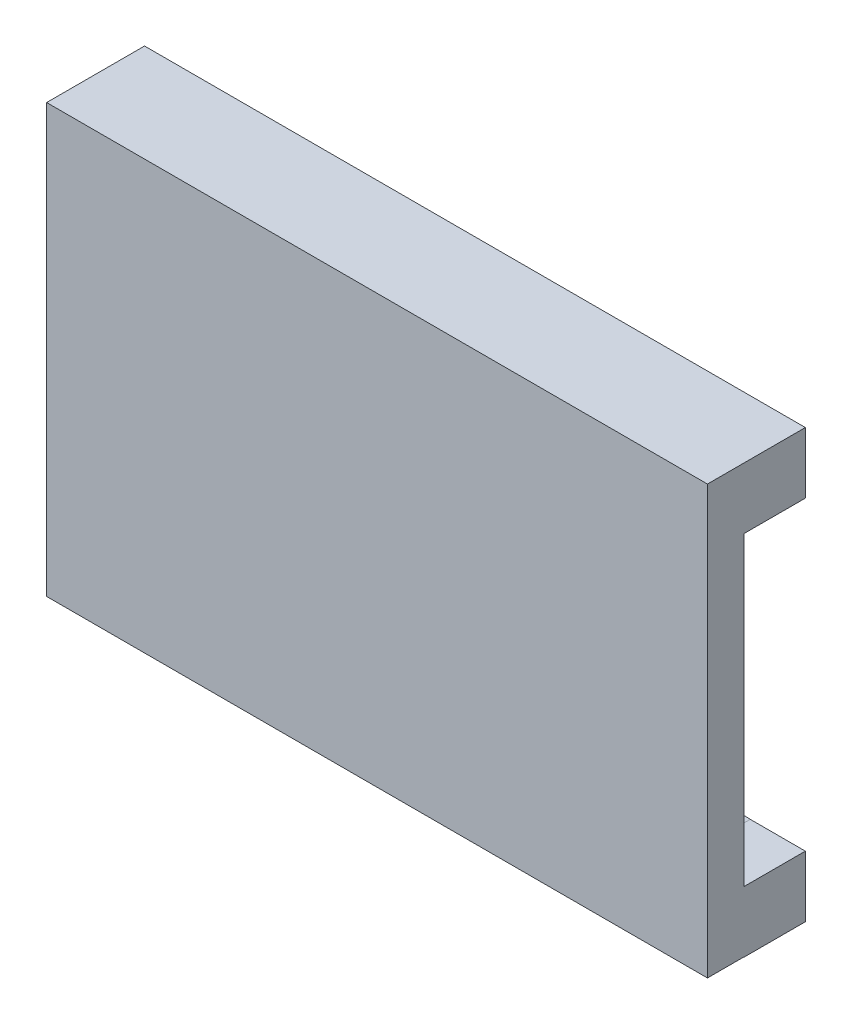
SolidWorks part; units mm, degrees
ref_plane "Front Plane" through (0, 0, 0) normal (0, 0, 1) x (1, 0, 0)
ref_plane "Top Plane" through (0, 0, 0) normal (0, 1, 0) x (1, 0, 0)
ref_plane "Right Plane" through (0, 0, 0) normal (1, 0, 0) x (0, 0, -1)
sketch "Sketch1" plane through (0, 0, 0) normal (0, 0, 1) x (1, 0, 0)
  line L0 (-7.25, 12.4789) -> (7.25, 12.4789) construction
  line L1 (27, -12.5) -> (-27, -12.5) construction
  line L2 (-27, 12.4789) -> (27, 12.4789)
  line L3 (27, -12.5) -> (-27, -12.5)
  line L4 (27, -12.5) -> (27, 12.4789)
  line L5 (-27, 12.4789) -> (-27, -12.5)
  circle A0 centre (-22.5, 0) radius 1.25 construction
  circle A1 centre (22.5, 0) radius 1.25 construction
  circle A2 centre (-22.5, 0) radius 1.25 construction
  circle A3 centre (22.5, 0) radius 1.25 construction
  circle A5 centre (-22.5, 0) radius 1.05
  circle A6 centre (22.5, 0) radius 1.05
  point P1 (0, 0)
  dimension "D1" = 0.2
extrude "Boss-Extrude1" add sketch "Sketch1" against normal blind 3 contours A5 | A6
extrude "Boss-Extrude2" add sketch "Sketch1<3>" along normal blind 3 contours L2 L4 L3 L5
sketch "Sketch1<3>" plane through (0, 0, 0) normal (0, 0, 1) x (1, 0, 0) same geometry as "Sketch1"
sketch "Sketch3" plane through (0, 0, 0) normal (0, 0, -1) x (-1, 0, 0)
  line L0 (-27, 12.4789) -> (-22.5, 12.4789)
  line L1 (27, 12.4789) -> (-27, 12.4789) construction
  line L2 (-22.5, 12.4789) -> (-1, 11.3522)
  line L4 (-22.5, 14.2313) -> (-1, 13.1046)
  line L7 (-22.5, 15.7313) -> (22.5, 15.7313)
  line L8 (-27, 12.4789) -> (-27, 17.4789)
  line L9 (27, 12.4789) -> (27, 17.4789)
  line L10 (22.5, 14.2313) -> (1, 13.1046)
  line L11 (22.5, 12.4789) -> (1, 11.3522)
  line L12 (27, 12.4789) -> (22.5, 12.4789)
  line L13 (27, 17.4789) -> (-27, 17.4789)
  line L14 (1, 11.3522) -> (1, 12.4789)
  line L15 (1, 12.4789) -> (1, 13.0522)
  line L16 (-27, -0.0105) -> (-13.4958, -0.0105)
  line L17 (-1, 12.4789) -> (-1, 13.0522)
  line L18 (-1, 13.1046) -> (-1, 11.3522)
  line L19 (1, 13.1046) -> (1, 11.3522)
  line L20 (-27, -12.5) -> (-27, 12.4789) construction
  line L21 (1, -13.1256) -> (1, -11.3732)
  line L22 (-1, -13.1256) -> (-1, -11.3732)
  line L23 (-1, -12.5) -> (-1, -13.0732)
  line L24 (1, -12.5) -> (1, -13.0732)
  line L25 (1, -11.3732) -> (1, -12.5)
  line L26 (27, -17.5) -> (-27, -17.5)
  line L27 (27, -12.5) -> (22.5, -12.5)
  line L28 (22.5, -12.5) -> (1, -11.3732)
  line L29 (22.5, -14.2524) -> (1, -13.1256)
  line L30 (27, -12.5) -> (27, -17.5)
  line L31 (-27, -12.5) -> (-27, -17.5)
  line L32 (-22.5, -15.7524) -> (22.5, -15.7524)
  line L33 (-22.5, -14.2524) -> (-1, -13.1256)
  line L34 (-22.5, -12.5) -> (-1, -11.3732)
  line L35 (-27, -12.5) -> (-22.5, -12.5)
  arc A0 (-22.5, 15.7313) -> (-22.5, 14.2313) centre (-22.5, 14.9813) ccw
  arc A1 (22.5, 15.7313) -> (22.5, 14.2313) centre (22.5, 14.9813) cw
  arc A2 (22.5, -15.7524) -> (22.5, -14.2524) centre (22.5, -15.0024) ccw
  arc A3 (-22.5, -15.7524) -> (-22.5, -14.2524) centre (-22.5, -15.0024) cw
  point P20 (0, 15.7313)
  point P50 (0, -15.7524)
  point P51 (0, 0)
  point P52 (0, 0)
  point P53 (0, 0)
  dimension "D1" = 3
  dimension "D2" = 1.75
  dimension "D3" = 1.5
  dimension "D4" = 5
sketch "Sketch4" plane through (0, 0, 3) normal (0, 0, 1) x (1, 0, 0)
  line L0 (-27, 12.4789) -> (-27, 17.4789)
  line L1 (-27, 17.4789) -> (27, 17.4789)
  line L2 (27, 17.4789) -> (27, 12.4789)
  line L3 (27, 12.4789) -> (-27, 12.4789)
  line L4 (0, 0) -> (-5.1925, 0)
  line L5 (27, -17.4789) -> (27, -12.4789)
  line L6 (-27, -17.4789) -> (27, -17.4789)
  line L7 (-27, -12.4789) -> (-27, -17.4789)
  line L8 (27, -12.4789) -> (-27, -12.4789)
extrude "Boss-Extrude4" add sketch "Sketch4" against normal up to vertex (3 mm away) contours L3 L0 L1 L2 | L5 L8 L7 L6 up to point (-27, 12.4789, 0)
extrude "Boss-Extrude5" add sketch "Sketch3" along normal blind 5 contours L11 L12 L9 L13 L8 L0 L2 L18 L4 A0 L7 A1 L10 L19
extrude "Boss-Extrude6" add sketch "Sketch3<4>" along normal blind 5 contours L28 L27 L30 L26 L31 L35 L34 L22 L33 A3 L32 A2 L29 L21
sketch "Sketch3<4>" plane through (0, 0, 0) normal (0, 0, -1) x (-1, 0, 0) same geometry as "Sketch3"
sketch "Sketch6" plane through (0, 12.4789, 0) normal (0, -1, 0) x (1, 0, 0)
  line L0 (22.5, -1) -> (-22.5, -1)
  line L1 (22.5, -5) -> (22.5, 0) construction
  line L2 (-22.5, -5) -> (-22.5, 0) construction
  line L3 (22.5, 0) -> (-22.5, 0) construction
  line L4 (22.5, -1) -> (22.5, 0)
  line L5 (22.5, 0) -> (-22.5, 0)
  line L6 (-22.5, 0) -> (-22.5, -1)
  dimension "D1" = 1
extrude "Cut-Extrude1" cut sketch "Sketch6" against normal mid plane 5
sketch "Sketch7" plane through (0, -12.5, 0) normal (0, 1, 0) x (1, 0, 0)
  line L0 (-22.5, 1) -> (22.5, 1)
  line L1 (-22.5, 5) -> (-22.5, 0) construction
  line L2 (22.5, 5) -> (22.5, 0) construction
  line L3 (22.5, 0) -> (-22.5, 0) construction
  line L4 (-22.5, 1) -> (-22.5, 0)
  line L5 (-22.5, 0) -> (22.5, 0)
  line L6 (22.5, 0) -> (22.5, 1)
  point P8 (0, 0)
  dimension "D1" = 1
extrude "Cut-Extrude2" cut sketch "Sketch7" against normal mid plane 5
